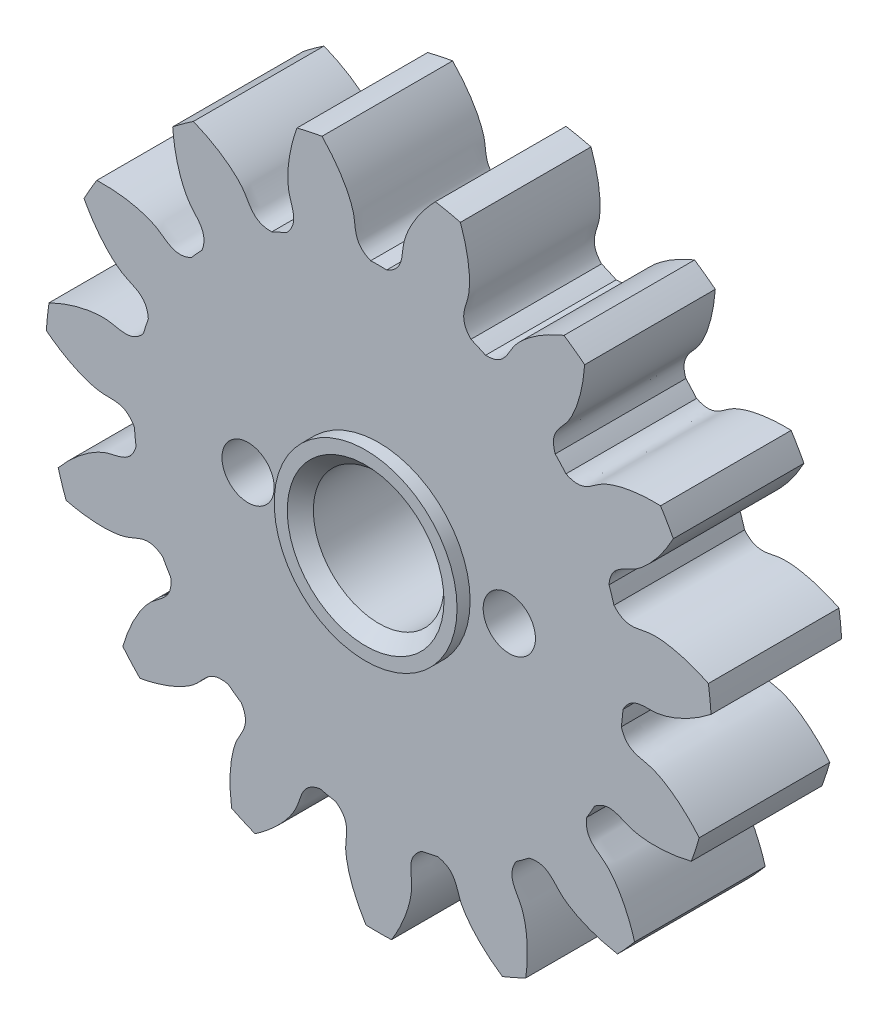
SolidWorks part; units mm, degrees
ref_plane "前视基准面" through (0, 0, 0) normal (0, 0, 1) x (1, 0, 0)
ref_plane "上视基准面" through (0, 0, 0) normal (0, 1, 0) x (1, 0, 0)
ref_plane "右视基准面" through (0, 0, 0) normal (1, 0, 0) x (0, 0, -1)
sketch "草图1" plane through (0, 0, 0) normal (0, 0, 1) x (1, 0, 0)
  circle A0 centre (0, 0) radius 12.75
extrude "凸台-拉伸1" add sketch "草图1" along normal blind 5
ref_axis "基准轴1" through (0, 0, -0.25) along (0, 0, 1)
sketch "草图2" plane through (0, 0, 0) normal (0, 0, 1) x (1, 0, 0)
  line L0 (0, 0) -> (0, 12.75) construction
  circle A0 centre (0, 0) radius 12.75 construction
  arc A1 (0.3064, 9.37) -> (-0.3064, 9.37) centre (0, 0) ccw
  arc A2 (4.8703, 14.4539) -> (-4.8703, 14.4539) centre (0, 0) ccw
  spline S0 degree 3 poles (0.3064, 9.37) (0.9858, 9.6516) (0.8582, 10.1795) (0.9769, 10.6628) (0.9861, 10.6975) (0.9973, 10.7361) (1.0104, 10.7785) (1.0257, 10.8247) (1.0434, 10.8745) (1.0635, 10.9279) (1.0863, 10.9848) (1.1118, 11.0452) (1.1403, 11.1089) (1.1718, 11.1759) (1.2066, 11.2459) (1.2447, 11.3191) (1.2863, 11.3952) (1.3315, 11.474) (1.3804, 11.5556) (1.4332, 11.6398) (1.49, 11.7265) (1.5509, 11.8155) (1.616, 11.9067) (1.6855, 11.9999) (1.7594, 12.0951) (1.8379, 12.1921) (1.921, 12.2907) (2.0088, 12.3909) (2.1015, 12.4924) (2.1991, 12.595) (2.3018, 12.6987) (2.4095, 12.8033) (2.5223, 12.9086) (2.6404, 13.0144) (2.7638, 13.1206) (2.8926, 13.227) (3.0268, 13.3335) (3.1664, 13.4398) (3.3116, 13.5458) (3.4623, 13.6512) (3.6186, 13.7561) (3.7805, 13.86) (3.948, 13.9629) (4.1213, 14.0646) (4.3002, 14.1648) (4.5489, 14.2977) (4.7402, 14.3926) (4.8703, 14.4539) knots 0 0 0 0 0.202473 0.206979 0.212085 0.217793 0.224101 0.23101 0.23852 0.24663 0.255341 0.264653 0.274566 0.285079 0.296194 0.307909 0.320225 0.333141 0.346659 0.360777 0.375496 0.390816 0.406736 0.423257 0.440379 0.458102 0.476426 0.49535 0.514875 0.535001 0.555728 0.577055 0.598984 0.621513 0.644642 0.668373 0.692704 0.717636 0.743169 0.769303 0.796037 0.823373 0.851309 0.879845 0.908983 0.938721 1 1 1 1
  spline S1 degree 3 poles (-0.3064, 9.37) (-0.9858, 9.6516) (-0.8582, 10.1795) (-0.9769, 10.6628) (-0.9861, 10.6975) (-0.9973, 10.7361) (-1.0104, 10.7785) (-1.0257, 10.8247) (-1.0434, 10.8745) (-1.0635, 10.9279) (-1.0863, 10.9848) (-1.1118, 11.0452) (-1.1403, 11.1089) (-1.1718, 11.1759) (-1.2066, 11.2459) (-1.2447, 11.3191) (-1.2863, 11.3952) (-1.3315, 11.474) (-1.3804, 11.5556) (-1.4332, 11.6398) (-1.49, 11.7265) (-1.5509, 11.8155) (-1.616, 11.9067) (-1.6855, 11.9999) (-1.7594, 12.0951) (-1.8379, 12.1921) (-1.921, 12.2907) (-2.0088, 12.3909) (-2.1015, 12.4924) (-2.1991, 12.595) (-2.3018, 12.6987) (-2.4095, 12.8033) (-2.5223, 12.9086) (-2.6404, 13.0144) (-2.7638, 13.1206) (-2.8926, 13.227) (-3.0268, 13.3335) (-3.1664, 13.4398) (-3.3116, 13.5458) (-3.4623, 13.6512) (-3.6186, 13.7561) (-3.7805, 13.86) (-3.948, 13.9629) (-4.1213, 14.0646) (-4.3002, 14.1648) (-4.5489, 14.2977) (-4.7402, 14.3926) (-4.8703, 14.4539) knots 0 0 0 0 0.202473 0.206979 0.212085 0.217793 0.224101 0.23101 0.23852 0.24663 0.255341 0.264653 0.274566 0.285079 0.296194 0.307909 0.320225 0.333141 0.346659 0.360777 0.375496 0.390816 0.406736 0.423257 0.440379 0.458102 0.476426 0.49535 0.514875 0.535001 0.555728 0.577055 0.598984 0.621513 0.644642 0.668373 0.692704 0.717636 0.743169 0.769303 0.796037 0.823373 0.851309 0.879845 0.908983 0.938721 1 1 1 1
extrude "切除-拉伸1" cut sketch "草图2" along normal through all
pattern_circular "阵列(圆周)1" count 15 over 360 about axis through (0, 0, -0.25) along (0, 0, 1) of "切除-拉伸1"
sketch "草图3" plane through (0, 0, 0) normal (0, 0, 1) x (1, 0, 0)
  circle A0 centre (0, 0) radius 11.25 construction
  dimension "Dn" = 22.5
sketch "草图4" plane through (0, 0, 5) normal (0, 0, 1) x (1, 0, 0)
  circle A0 centre (0, 0) radius 2.5
  dimension "D1" = 5
extrude "切除-拉伸2" cut sketch "草图4" against normal through all
sketch "草图7" plane through (0, 0, 5) normal (0, 0, 1) x (1, 0, 0)
  circle A0 centre (0, 0) radius 3.5
  circle A1 centre (0, 0) radius 2.5 construction
  circle A2 centre (0, 0) radius 2.5
  dimension "D1" = 7
extrude "凸台-拉伸2" add sketch "草图7" along normal blind 0.5
chamfer "倒角1" distance 0.5 angle 45 2 edges at (2.5, 0, 0) (2.5, 0, 5.5)
hole_wizard "大小mm Transitional 暗销孔1" positions "草图5" profile "草图6" hole size "Ø2.0" standard "GB" end condition through all
sketch "草图5" plane through (0, 0, 5) normal (0, 0, 1) x (1, 0, 0)
  line L1 (0, -4.5908) -> (0, 0) construction
  point P0 (5, 0)
  point P2 (-5, 0)
  dimension "D1" = 5
sketch "草图6" plane through (5, 0, 5) normal (1, 0, 0) x (0, -1, 0)
  line L0 (0, 0) -> (0, 5)
  line L1 (0, 5) -> (1, 5)
  line L2 (1, 5) -> (1, 0)
  line L5 (1, 0) -> (0, 0)
  line L11 (0, -6.35) -> (0, 107.95) construction
  dimension "通孔孔直径" = 2
  dimension "通孔孔深度" = 5
